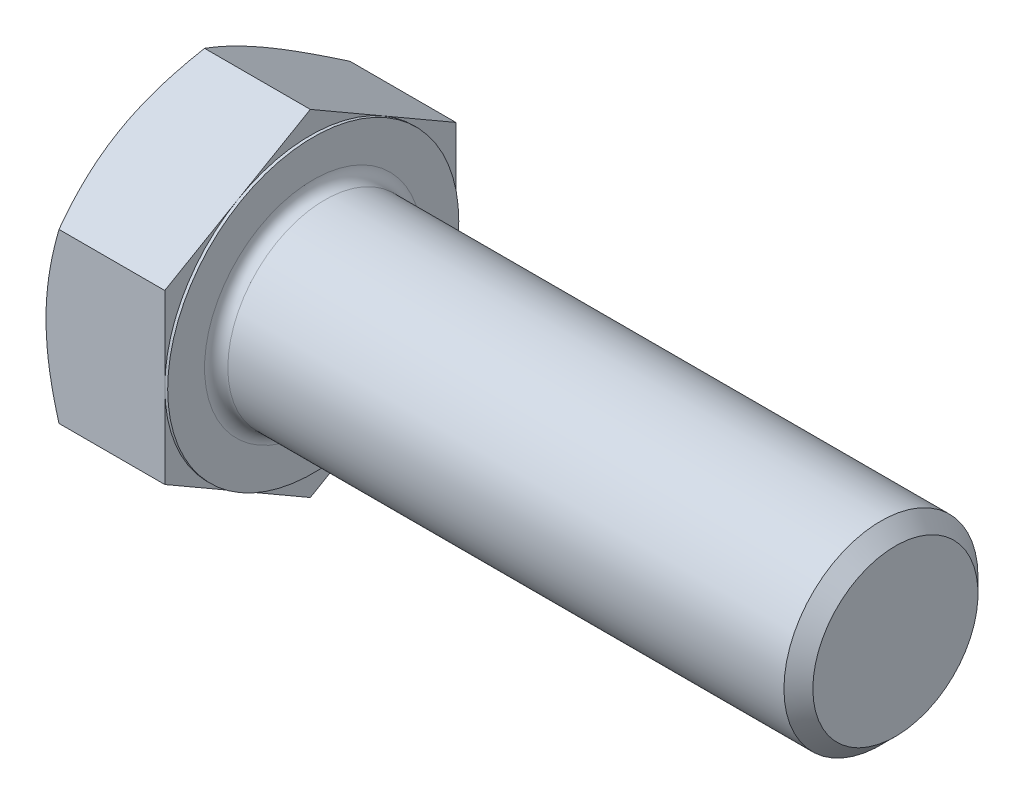
SolidWorks part; units mm, degrees
extrude "BaseHead" add sketch "Sketch1" along normal blind 15.9258
sketch "Sketch1" plane through (0, 0, 0) normal (1, 0, 0) x (0, 0, -1)
  line L0 (19.05, 10.9985) -> (19.05, -10.9985)
  line L1 (-19.05, 10.9985) -> (-19.05, -10.9985)
  line L2 (19.05, -10.9985) -> (0, -21.997)
  line L3 (0, -21.997) -> (-19.05, -10.9985)
  line L4 (19.05, 10.9985) -> (0, 21.997)
  line L5 (0, 21.997) -> (-19.05, 10.9985)
  dimension "D2" = 120
  dimension "D3" = 19.05
  dimension "D4" = 19.05
  dimension "D5" = 19.05
revolve "HeadChamfer" cut sketch "Sketch3" angle 360 about L6 other way angle 60
sketch "Sketch3" plane through (0, 0, 0) normal (0, 0, 1) x (1, 0, 0)
  line L0 (0, 19.05) -> (5.3677, 28.347)
  line L1 (0, 21.997) -> (0, 10.9985) construction
  line L2 (5.3677, 28.347) -> (5.3677, 34.697)
  line L3 (5.3677, 34.697) -> (-12.7, 34.697)
  line L4 (-12.7, 34.697) -> (-12.7, 19.05)
  line L5 (-12.7, 19.05) -> (0, 19.05)
  line L6 (0, 0) -> (99.06, 0) construction
  line L7 (15.9258, 21.997) -> (0, 21.997) construction
  dimension "D1" = 19.05
  dimension "D2" = 6.35
  dimension "D3" = 12.7
  dimension "D4" = 6.35
  dimension "Head_ch_ang" = 30
ref_plane "Plane1" through (0, 0, 0) normal (0, 0, 1) x (1, 0, 0)
ref_plane "Plane2" through (0, 0, 0) normal (0, 1, 0) x (1, 0, 0)
ref_plane "Plane3" through (0, 0, 0) normal (1, 0, 0) x (0, 0, -1)
sketch "BodySke" plane through (0, 0, 0) normal (0, 0, 1) x (1, 0, 0)
  line L0 (0, 10.9985) -> (0, -10.9985) construction
  line L1 (0, 0) -> (92.1258, 0)
  line L2 (0, 0) -> (0, 12.7)
  line L3 (0, 12.7) -> (90.2335, 12.7)
  line L4 (92.1258, 0) -> (92.1258, 10.8077)
  line L5 (15.9258, 21.997) -> (15.9258, 10.9985) construction
  line L6 (92.1258, 10.8077) -> (90.2335, 12.7)
  line L7 (0, 0) -> (96.52, 0) construction
  line L8 (92.1258, -10.8077) -> (90.2335, -12.7) construction
  line L9 (0, -12.7) -> (90.2335, -12.7) construction
  line L10 (18.034, 15.24) -> (18.034, -1.27) construction
  line L11 (60.3758, 15.24) -> (60.3758, -1.27) construction
  line L12 (15.9258, 10.9985) -> (15.9258, -10.9985) construction
  dimension "Diameter" = 25.4
revolve "BaseBody" add sketch "BodySke" angle 360 about L7
cosmetic thread "ThreadCosmetic" [suppressed] parameters "Thread_length"=31.75, "Thread_minor"=21.6154
sketch "Sketch4" plane through (0, 0, 0) normal (0, 0, 1) x (1, 0, 0)
  line L1 (15.9258, 21.997) -> (15.9258, 10.9985) construction
  line L2 (15.9258, 19.05) -> (15.5448, 19.05)
  line L3 (15.9258, 19.05) -> (15.9258, 47.397)
  line L4 (15.9258, 47.397) -> (15.5448, 47.397)
  line L5 (0, 0) -> (95.25, 0) construction
  line L6 (0, 0) -> (96.52, 0) construction
  line L7 (15.5448, 19.05) -> (15.5448, 47.397)
  line L8 (15.9258, 21.997) -> (1.7015, 21.997) construction
  dimension "D1" = 19.05
  dimension "D2" = 25.4
revolve "BearingFace" cut sketch "Sketch4" angle 360 about L5
fillet "HeadFillet" radius 1.524 1 edges at (15.9258, 0, -12.7)
sketch "ThdSchSke" plane through (0, 0, 0) normal (0, 0, 1) x (1, 0, 0)
  line L0 (60.3758, -10.8077) -> (59.0508, -12.7)
  line L1 (60.3758, -10.8077) -> (61.7008, -12.7)
  line L2 (61.7008, -12.7) -> (61.7008, -15.875)
  line L3 (-3.175, 0) -> (5.1513, 0) construction
  line L5 (61.7008, -15.875) -> (59.0508, -15.875)
  line L6 (59.0508, -15.875) -> (59.0508, -12.7)
  dimension "Thread_minor" = 21.6154
  dimension "Diameter" = 25.4
  dimension "Start" = 60.3758
revolve "ThreadSchematic" [suppressed] cut sketch "ThdSchSke" angle 360 about L3
pattern_linear "ThdSchPat" [suppressed]
equation "\"D3@Sketch1\" = \"Width_flats@Sketch1\" / 2"
equation "\"D4@Sketch1\" = \"D3@Sketch1\""
equation "\"D5@Sketch1\" = \"D4@Sketch1\""
equation "\"Thread_minor@ThreadCosmetic\" = \"Minor_dia@BodySke\""
equation "\"D1@Sketch3\" = \"Width_flats@Sketch1\" / 2"
equation "\"D1@Sketch4\" = \"Width_flats@Sketch1\" / 2"
equation "\"Thread_length@ThreadCosmetic\" = ((sgn( (\"Length@BodySke\" - \"Advance@BodySke\" ) - \"Thread_nom@BodySke\" )-1)*( (\"Length@BodySke\" - \"Advance@BodySke\" ) - \"Thread_nom@BodySke\" ))/-2+ \"Thread_nom@BodySke\""
equation "\"Thread_minor@ThdSchSke\" = \"Minor_dia@BodySke\""
equation "\"Diameter@ThdSchSke\" = \"Diameter@BodySke\""
equation "\"Overcut@ThdSchSke\" = \"Diameter@BodySke\" * 1.25"
equation "\"Start@ThdSchSke\" = \"Head_ht@BaseHead\" + \"Length@BodySke\" - \"Thread_length@ThreadCosmetic\"  '---Non-countersunk---"
equation "\"Num_threads@ThdSchPat\" = int( \"Thread_length@ThreadCosmetic\" / \"Advance@BodySke\" + 0.999 )  + 1"
equation "\"Advance@ThdSchPat\" = \"Thread_length@ThreadCosmetic\" /  (\"Num_threads@ThdSchPat\" - 1) 'relax it"
equation "\"Num_threads@ThdSchPat\" = \"Num_threads@ThdSchPat\" - sgn( \"Num_threads@ThdSchPat\" - 1) '---chamfered tips only---"
